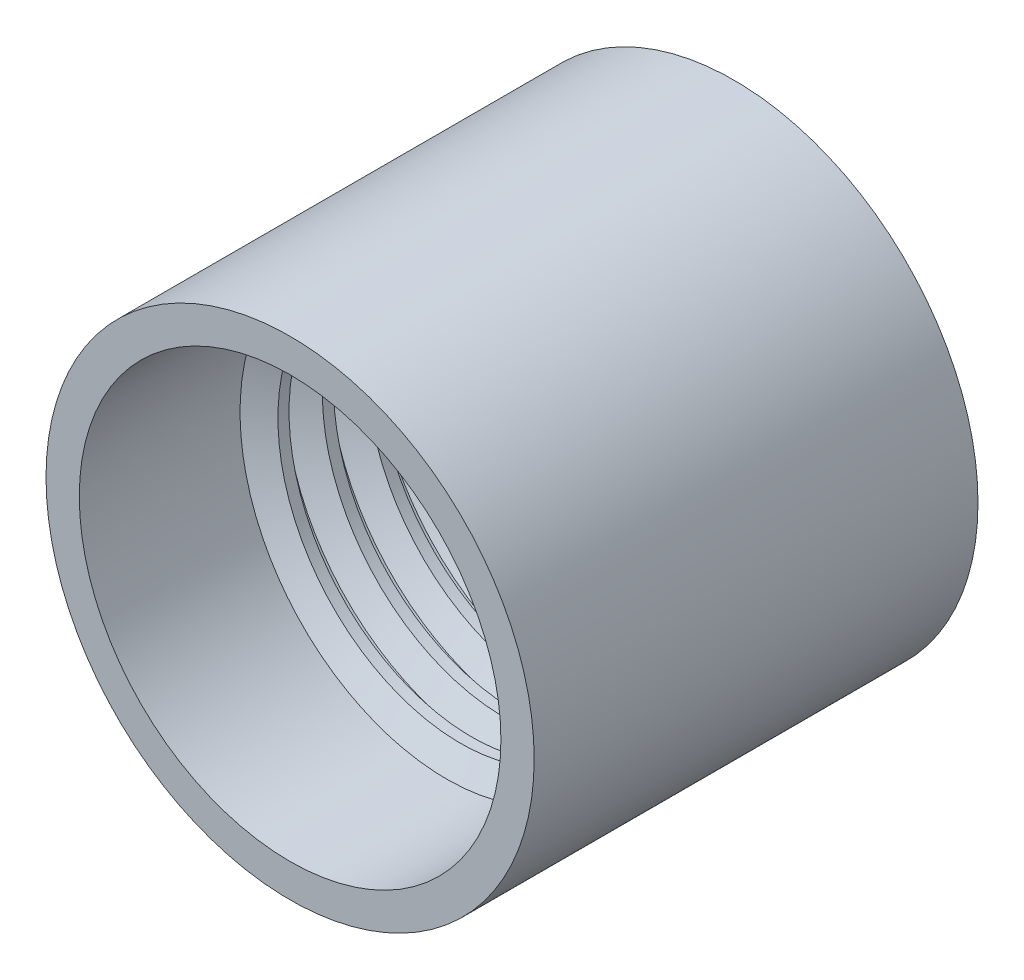
SolidWorks part; units mm, degrees
ref_plane "前视基准面" through (0, 0, 0) normal (0, 0, 1) x (1, 0, 0)
ref_plane "上视基准面" through (0, 0, 0) normal (0, 1, 0) x (1, 0, 0)
ref_plane "右视基准面" through (0, 0, 0) normal (1, 0, 0) x (0, 0, -1)
sketch "草图1" plane through (0, 0, 0) normal (0, 0, 1) x (1, 0, 0)
  circle A0 centre (0, 0) radius 19
  circle A1 centre (0, 0) radius 22
  dimension "D1" = 38
  dimension "D2" = 44
extrude "凸台-拉伸1" add sketch "草图1" along normal blind 40
thread "螺纹线1" pitch 4 method extrude profile "螺纹线轮廓1" start angle 0, offset 0, length 25, pitch 4, diameter 38
ref_plane "基准面1" through (19, 0, 0) normal (0, -1, 0) x (1, 0, 0)
sketch "螺纹线轮廓1" plane through (19, 0, 0) normal (0, -1, 0) x (1, 0, 0)
  line L0 (0, 0) -> (0, 4) construction
  line L11 (0, 0) -> (0, 3.5)
  line L12 (0, 3.5) -> (-2.1651, 2.25)
  line L13 (-2.1651, 2.25) -> (-2.1651, 1.25)
  line L15 (-2.1651, 1.25) -> (0, 0)
  line L17 (-2.1651, 1.75) -> (0, 1.75) construction
  point P2 (0, 0)
  dimension "Pitch" = 4
  dimension "Profile_Angle" = 60
  dimension "Profile_Land" = 1
  dimension "Profile_Height" = 2.1651
